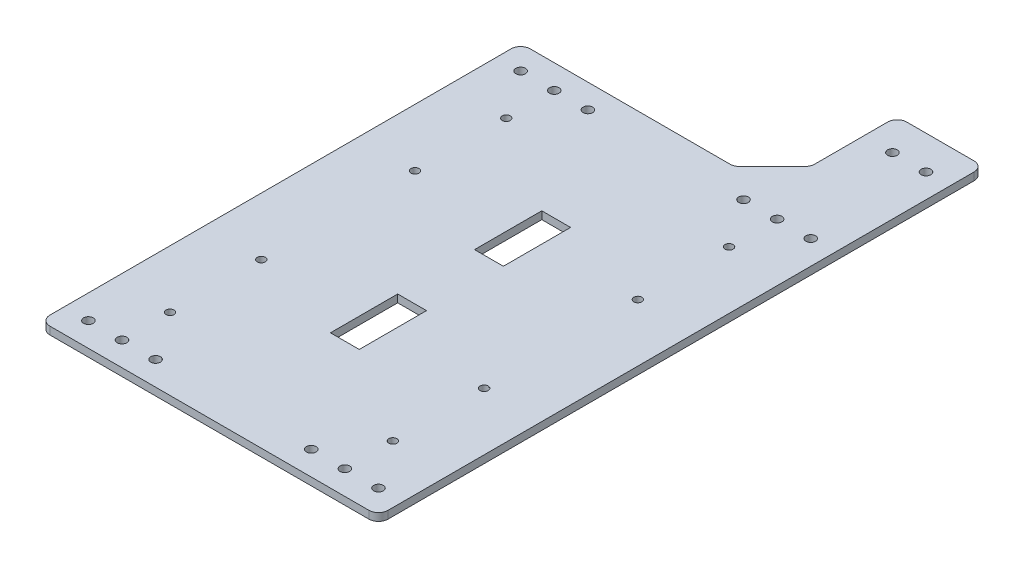
SolidWorks part; units mm, degrees
material "3.3549 (EN-AW 5182)"
ref_plane "Front Plane" through (0, 0, 0) normal (0, 0, 1) x (1, 0, 0)
ref_plane "Top Plane" through (0, 0, 0) normal (0, 1, 0) x (1, 0, 0)
ref_plane "Right Plane" through (0, 0, 0) normal (1, 0, 0) x (0, 0, -1)
sketch "Sketch1" plane through (0, 0, 0) normal (0, 1, 0) x (1, 0, 0)
  line L1 (-123, 125) -> (8, 125)
  line L2 (-123, 125) -> (-123, -125)
  line L3 (-53, -125) -> (53, -125)
  line L4 (53, 125) -> (53, -125)
  line L7 (53, 125) -> (53, 190)
  line L8 (53, 190) -> (8, 190)
  line L9 (8, 190) -> (8, 125)
  line L10 (-123, -125) -> (-53, -125)
  point P4 (0, -125)
  point P5 (-123, 0)
  dimension "D1" = 176
  dimension "D2" = 250
  dimension "D3" = 65
  dimension "D4" = 45
extrude "Boss-Extrude1" add sketch "Sketch1" along normal blind 4
sketch "Sketch2" plane through (0, 4, 0) normal (0, 1, 0) x (1, 0, 0)
  line L0 (-57.5, 125) -> (-57.5, -125) construction
  line L1 (8, 125) -> (-123, 125) construction
  line L2 (-123, -125) -> (53, -125) construction
  line L3 (0, 0) -> (78, 0) construction
  line L4 (-123, 125) -> (-123, -125) construction
  line L5 (53, -125) -> (53, 190) construction
  line L6 (-75.5, -112.5) -> (-110.5, -112.5) construction
  line L8 (5.5, -112.5) -> (40.5, -112.5) construction
  line L9 (5.5, 112.5) -> (40.5, 112.5) construction
  line L11 (-75.5, 112.5) -> (-110.5, 112.5) construction
  circle A0 centre (-110.5, -112.5) radius 2.5
  circle A1 centre (-75.5, -112.5) radius 2.5
  circle A8 centre (-93, -112.5) radius 2.5
  circle A12 centre (-93, -87.5) radius 2.1
  circle A16 centre (5.5, -112.5) radius 2.5
  circle A17 centre (23, -112.5) radius 2.5
  circle A18 centre (40.5, -112.5) radius 2.5
  circle A19 centre (23, -87.5) radius 2.1
  circle A20 centre (23, 87.5) radius 2.1
  circle A21 centre (40.5, 112.5) radius 2.5
  circle A22 centre (23, 112.5) radius 2.5
  circle A23 centre (5.5, 112.5) radius 2.5
  circle A24 centre (-93, 87.5) radius 2.1
  circle A25 centre (-93, 112.5) radius 2.5
  circle A26 centre (-75.5, 112.5) radius 2.5
  circle A27 centre (-110.5, 112.5) radius 2.5
  circle A30 centre (40.5, 172.5) radius 2.5
  circle A31 centre (23, 172.5) radius 2.5
  dimension "D1" = 5
  dimension "D6" = 4.2
  dimension "D7" = 12.5
  dimension "D9" = 60
  dimension "D2" = 12.5
  dimension "D3" = 35
  dimension "D4" = 12.5
  dimension "D5" = 25
  dimension "D8" = 25
extrude "Cut-Extrude1" cut sketch "Sketch2" against normal through all
sketch "Sketch3" plane through (0, 0, 0) normal (0, -1, 0) x (1, 0, 0)
  line L0 (-123, 125) -> (53, 125) construction
  line L1 (-42, 55) -> (-27, 55)
  line L2 (-42, 55) -> (-42, 20)
  line L3 (-42, 20) -> (-27, 20)
  line L4 (-27, 55) -> (-27, 20)
  line L5 (53, 0) -> (-123, 0) construction
  line L6 (53, 125) -> (53, -190) construction
  line L7 (-123, -125) -> (-123, 125) construction
  line L8 (-27, -55) -> (-27, -20)
  line L9 (-42, -20) -> (-27, -20)
  line L10 (-42, -55) -> (-42, -20)
  line L11 (-42, -55) -> (-27, -55)
  line L12 (53, 125) -> (53, -190) construction
  point P16 (-123, 0)
  dimension "D1" = 70
  dimension "D2" = 35
  dimension "D3" = 15
  dimension "D4" = 80
extrude "Cut-Extrude2" cut sketch "Sketch3" against normal through all contours L10 L11 L8 L3 | L2 L9 L4 L1 region at (-34.5, 0, 37.5) region at (-34.5, 0, -37.5)
sketch "Sketch4" plane through (0, 0, 0) normal (0, -1, 0) x (1, 0, 0)
  line L0 (-103, 0) -> (53, 0) construction
  line L3 (2.0229, 0) -> (-35, 0) construction
  line L4 (-35, 0) -> (-35, 125) construction
  line L6 (-93, 87.5) -> (-93, -87.5) construction
  line L7 (-123, -125) -> (-123, 125) construction
  line L8 (53, 125) -> (53, -190) construction
  circle A0 centre (-93, 40) radius 2.1
  circle A25 centre (-93, -40) radius 2.1
  circle A26 centre (23, -40) radius 2.1
  circle A29 centre (23, 40) radius 2.1
  circle A30 centre (-93, -87.5) radius 2.1 construction
  dimension "D1" = 4.2
  dimension "D2" = 40
extrude "Cut-Extrude3" cut sketch "Sketch4" against normal blind 10
chamfer "Chamfer1" distance 20 angle 45 1 edges at (8, 2, -125)
fillet "Fillet1" radius 5 7 edges at (53, 2, 125) (-123, 2, 125) (-123, 2, -125) (53, 2, -190) (8, 2, -190) (-12, 2, -125) (8, 2, -145)
ref_plane "Plane3" through (-35, 0, 0) normal (-1, 0, 0) x (0, 0, 1)
